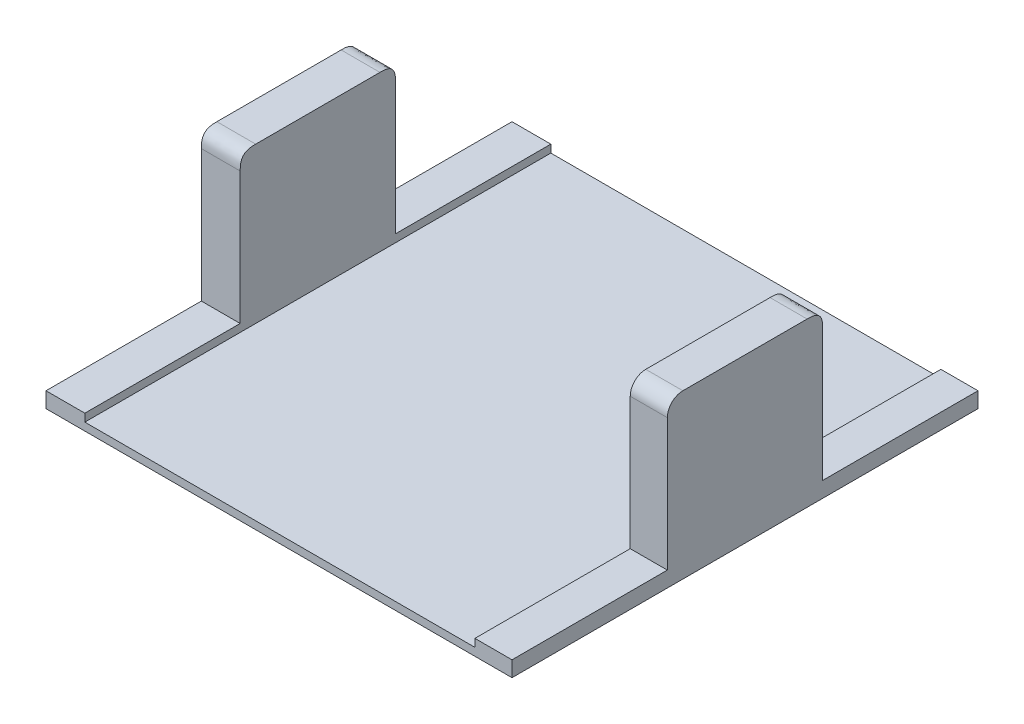
SolidWorks part; units mm, degrees
other "Marcação1"
sketch "Esboço7" plane through (-0.05, 200.05, 0) normal (-0.418, 0.221, 0.8811) x (0.8907, -0.0909, 0.4454)
ref_plane "Plano frontal" through (0, 0, 0) normal (0, 0, 1) x (1, 0, 0)
ref_plane "Plano superior" through (0, 0, 0) normal (0, 1, 0) x (1, 0, 0)
ref_plane "Plano direito" through (0, 0, 0) normal (1, 0, 0) x (0, 0, -1)
sketch "Esboço1" plane through (0, 0, 0) normal (0, 1, 0) x (1, 0, 0)
  line L1 (0, 0) -> (600, 0)
  line L2 (0, 0) -> (0, 600)
  line L3 (0, 600) -> (600, 600)
  line L4 (600, 0) -> (600, 600)
  line L5 (0, 0) -> (50, 0)
  line L6 (0, 0) -> (0, 600)
  line L7 (0, 600) -> (50, 600)
  line L8 (50, 0) -> (50, 600)
  line L9 (600, 0) -> (552.2278, 0)
  line L10 (600, 0) -> (600, 600)
  line L11 (600, 600) -> (552.2278, 600)
  line L12 (552.2278, 0) -> (552.2278, 600)
  dimension "D1" = 600
  dimension "D2" = 600
extrude "Ressalto-extrusão1" add sketch "Esboço1" along normal blind 200 contours L1 L8 L3 L2 | L12 L1 L4 L3 region at (25, 0, -300) region at (576.1139, 0, -300)
sketch "Esboço4" plane through (0, 200, 0) normal (0, 1, 0) x (1, 0, 0)
  line L1 (600, 0) -> (0, 0)
  line L2 (600, 0) -> (600, 600)
  line L3 (600, 600) -> (0, 600)
  line L4 (0, 0) -> (0, 600)
extrude "Ressalto-extrusão4" add sketch "Esboço4" along normal blind 10 from offset 210 offset against normal yes
sketch "Esboço5" plane through (600, 0, 0) normal (1, 0, 0) x (0, 0, -1)
  line L1 (0, 200) -> (200, 200)
  line L2 (0, 200) -> (0, 10)
  line L3 (0, 10) -> (200, 10)
  line L4 (200, 200) -> (200, 10)
extrude "Corte-extrusão1" cut sketch "Esboço5" against normal through all
sketch "Esboço6" plane through (600, 0, 0) normal (1, 0, 0) x (0, 0, -1)
  line L1 (600, 200) -> (400, 200)
  line L2 (600, 200) -> (600, 10)
  line L3 (600, 10) -> (400, 10)
  line L4 (400, 200) -> (400, 10)
  dimension "D1" = 200
extrude "Corte-extrusão2" cut sketch "Esboço6" against normal blind 600
fillet "Filete2" radius 20 1 edges at (576.1139, 200, -200)
fillet "Filete3" radius 20 1 edges at (576.1139, 200, -400) curvature continuous yes
fillet "Filete4" radius 20 1 edges at (25, 200, -200) curvature continuous yes
fillet "Filete5" radius 20 1 edges at (25, 200, -400) curvature continuous yes
